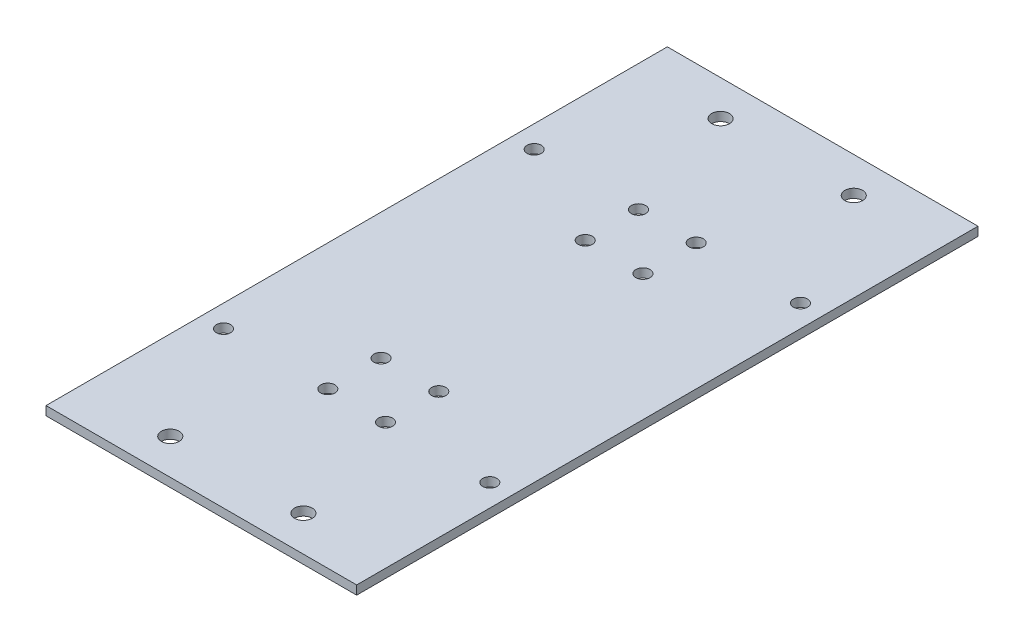
SolidWorks part; units mm, degrees
ref_plane "前基準面" through (0, 0, 0) normal (0, 0, 1) x (1, 0, 0)
ref_plane "上基準面" through (0, 0, 0) normal (0, 1, 0) x (1, 0, 0)
ref_plane "右基準面" through (0, 0, 0) normal (1, 0, 0) x (0, 0, -1)
sketch "草圖2" plane through (0, 0, 0) normal (0, 1, 0) x (1, 0, 0)
  line L1 (-35, -70) -> (35, -70)
  line L2 (-35, -70) -> (-35, 70)
  line L3 (-35, 70) -> (35, 70)
  line L4 (35, -70) -> (35, 70)
  line L5 (0, 70) -> (0, -70) construction
  line L6 (-35, 0) -> (35, 0) construction
  circle A0 centre (-6.5, 35) radius 1.6
  circle A1 centre (-6.5, -35) radius 1.6
  circle A2 centre (-6.5, 23) radius 1.6
  circle A3 centre (-6.5, -23) radius 1.6
  circle A4 centre (6.5, -35) radius 1.6
  circle A5 centre (6.5, -23) radius 1.6
  circle A6 centre (6.5, 23) radius 1.6
  circle A7 centre (6.5, 35) radius 1.6
  circle A8 centre (-30, 35) radius 1.6
  circle A9 centre (30, 35) radius 1.6
  circle A10 centre (-30, -35) radius 1.6
  circle A11 centre (30, -35) radius 1.6
  point P0 (0, 0)
  dimension "D4" = 3.2
  dimension "D9" = 3.2
  dimension "D1" = 140
  dimension "D2" = 70
  dimension "D3" = 58
  dimension "D5" = 13
  dimension "D6" = 12
  dimension "D7" = 70
  dimension "D8" = 60
extrude "填料-伸長1" add sketch "草圖2" along normal blind 2
sketch "草圖3" plane through (0, 2, 0) normal (0, 1, 0) x (1, 0, 0)
  line L0 (0, -75.2857) -> (0, 75.2857) construction
  line L1 (-75.5857, 0) -> (75.5857, 0) construction
  line L2 (-35, -70) -> (35, -70) construction
  circle A0 centre (-15, -62) radius 2
  circle A1 centre (-15, 62) radius 2
  circle A2 centre (15, -62) radius 2
  circle A3 centre (15, 62) radius 2
  point P4 (0, 0)
  point P7 (0, 0)
  point P15 (-15, -64.9493)
  point P16 (-15, -59.804)
  dimension "D2" = 4
  dimension "D1" = 30
  dimension "D3" = 8
extrude "除料-伸長1" cut sketch "草圖3" against normal through all
